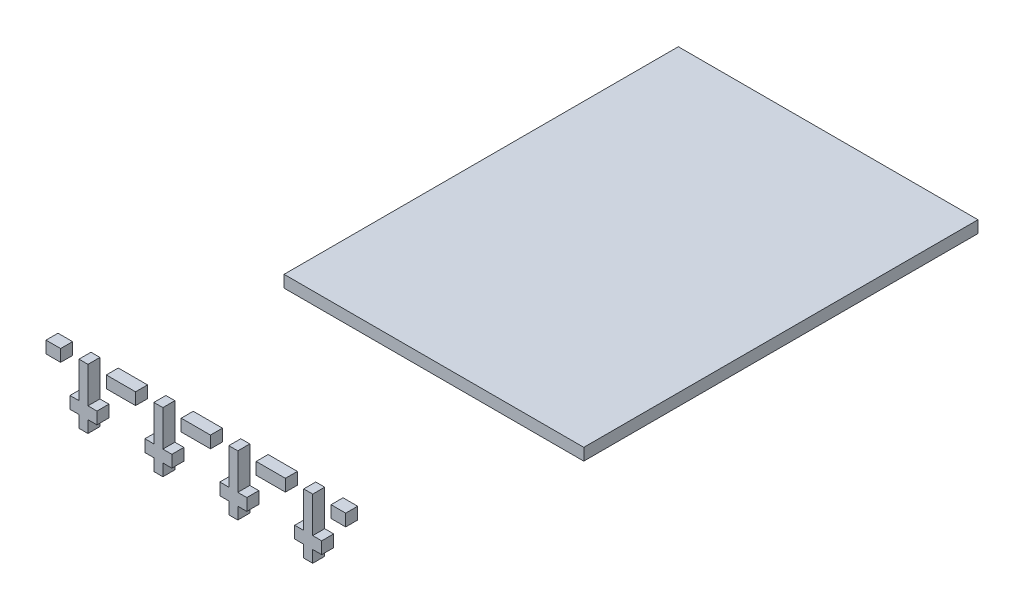
SolidWorks part; units mm, degrees
ref_plane "Front Plane" through (0, 0, 0) normal (0, 0, 1) x (1, 0, 0)
ref_plane "Top Plane" through (0, 0, 0) normal (0, 1, 0) x (1, 0, 0)
ref_plane "Right Plane" through (0, 0, 0) normal (1, 0, 0) x (0, 0, -1)
sketch "Sketch3" plane through (0, 0, 0) normal (0, 1, 0) x (1, 0, 0)
  line L0 (8.1353, -185.9578) -> (8.1353, -276.4821) construction
  line L1 (-16.8647, -185.9578) -> (-16.8647, -276.4821) construction
  line L2 (-16.8647, -222.3177) -> (83.1353, -222.3177)
  line L3 (-16.8647, -218.3177) -> (83.1353, -218.3177)
  line L4 (33.1353, -185.9578) -> (33.1353, -276.4821) construction
  line L5 (83.1353, -185.9578) -> (83.1353, -276.4821) construction
  line L6 (3.2529, -185.9578) -> (3.2529, -282.554) construction
  line L7 (-4.3647, -185.9578) -> (-4.3647, -282.554) construction
  line L8 (13.0176, -282.554) -> (13.0176, -185.9578) construction
  line L9 (28.2529, -185.9578) -> (28.2529, -282.554) construction
  line L10 (58.1353, -185.9578) -> (58.1353, -276.4821) construction
  line L11 (-16.8647, -220.3177) -> (83.1353, -220.3177) construction
  line L12 (38.0176, -282.554) -> (38.0176, -185.9578) construction
  line L13 (53.2529, -185.9578) -> (53.2529, -282.554) construction
  line L14 (20.6353, -282.554) -> (20.6353, -185.9578) construction
  line L15 (63.0176, -282.554) -> (63.0176, -185.9578) construction
  line L16 (78.2529, -185.9578) -> (78.2529, -282.554) construction
  line L17 (45.6353, -185.9578) -> (45.6353, -282.554) construction
  line L18 (-11.9824, -185.9578) -> (-11.9824, -282.554) construction
  line L19 (-2.8647, -222.3177) -> (-5.8647, -222.3177)
  line L20 (-2.8647, -222.3177) -> (-2.8647, -218.3177)
  line L21 (-2.8647, -218.3177) -> (-5.8647, -218.3177)
  line L22 (-5.8647, -222.3177) -> (-5.8647, -218.3177)
  line L23 (-2.8647, -222.3177) -> (-5.8647, -218.3177) construction
  line L24 (-2.8647, -218.3177) -> (-5.8647, -222.3177) construction
  line L25 (22.1353, -222.3177) -> (19.1353, -222.3177)
  line L26 (22.1353, -222.3177) -> (22.1353, -218.3177)
  line L27 (22.1353, -218.3177) -> (19.1353, -218.3177)
  line L28 (19.1353, -222.3177) -> (19.1353, -218.3177)
  line L29 (22.1353, -222.3177) -> (19.1353, -218.3177) construction
  line L30 (22.1353, -218.3177) -> (19.1353, -222.3177) construction
  line L31 (70.6353, -185.9578) -> (70.6353, -282.554) construction
  line L32 (-16.8647, -218.3177) -> (-16.8647, -222.3177)
  line L33 (47.1353, -222.3177) -> (44.1353, -222.3177)
  line L34 (47.1353, -222.3177) -> (47.1353, -218.3177)
  line L35 (47.1353, -218.3177) -> (44.1353, -218.3177)
  line L36 (44.1353, -222.3177) -> (44.1353, -218.3177)
  line L37 (47.1353, -222.3177) -> (44.1353, -218.3177) construction
  line L38 (47.1353, -218.3177) -> (44.1353, -222.3177) construction
  line L39 (72.1353, -222.3177) -> (69.1353, -222.3177)
  line L40 (72.1353, -222.3177) -> (72.1353, -218.3177)
  line L41 (72.1353, -218.3177) -> (69.1353, -218.3177)
  line L42 (69.1353, -222.3177) -> (69.1353, -218.3177)
  line L43 (72.1353, -222.3177) -> (69.1353, -218.3177) construction
  line L44 (72.1353, -218.3177) -> (69.1353, -222.3177) construction
  line L45 (-11.9824, -218.3177) -> (-11.9824, -222.3177)
  line L46 (3.2529, -218.3177) -> (3.2529, -222.3177)
  line L47 (13.0176, -218.3177) -> (13.0176, -222.3177)
  line L48 (28.2529, -218.3177) -> (28.2529, -222.3177)
  line L49 (38.0176, -218.3177) -> (38.0176, -222.3177)
  line L50 (53.2529, -218.3177) -> (53.2529, -222.3177)
  line L51 (63.0176, -218.3177) -> (63.0176, -222.3177)
  line L52 (78.2529, -218.3177) -> (78.2529, -222.3177)
  line L53 (83.1353, -218.3177) -> (83.1353, -222.3177)
  line L55 (-2.8647, -218.3177) -> (0.1353, -218.3177)
  line L56 (-2.8647, -218.3177) -> (-2.8647, -222.3177)
  line L57 (-2.8647, -222.3177) -> (0.1353, -222.3177)
  line L58 (0.1353, -218.3177) -> (0.1353, -222.3177)
  line L59 (-1.3647, -222.3177) -> (-1.3647, -218.3177) construction
  line L60 (-2.8647, -220.3177) -> (0.1353, -220.3177) construction
  line L61 (-5.8647, -218.3177) -> (-8.8647, -218.3177)
  line L62 (-5.8647, -218.3177) -> (-5.8647, -222.3177)
  line L63 (-5.8647, -222.3177) -> (-8.8647, -222.3177)
  line L64 (-8.8647, -218.3177) -> (-8.8647, -222.3177)
  line L65 (-7.3647, -222.3177) -> (-7.3647, -218.3177) construction
  line L66 (-5.8647, -220.3177) -> (-8.8647, -220.3177) construction
  line L67 (19.1353, -218.3177) -> (16.1353, -218.3177)
  line L68 (19.1353, -218.3177) -> (19.1353, -222.3177)
  line L69 (19.1353, -222.3177) -> (16.1353, -222.3177)
  line L70 (16.1353, -218.3177) -> (16.1353, -222.3177)
  line L71 (17.6353, -222.3177) -> (17.6353, -218.3177) construction
  line L72 (19.1353, -220.3177) -> (16.1353, -220.3177) construction
  line L73 (22.1353, -218.3177) -> (25.1353, -218.3177)
  line L74 (22.1353, -218.3177) -> (22.1353, -222.3177)
  line L75 (22.1353, -222.3177) -> (25.1353, -222.3177)
  line L76 (25.1353, -218.3177) -> (25.1353, -222.3177)
  line L77 (23.6353, -222.3177) -> (23.6353, -218.3177) construction
  line L78 (22.1353, -220.3177) -> (25.1353, -220.3177) construction
  line L79 (44.1353, -218.3177) -> (41.1353, -218.3177)
  line L80 (44.1353, -218.3177) -> (44.1353, -222.3177)
  line L81 (44.1353, -222.3177) -> (41.1353, -222.3177)
  line L82 (41.1353, -218.3177) -> (41.1353, -222.3177)
  line L83 (42.6353, -222.3177) -> (42.6353, -218.3177) construction
  line L84 (44.1353, -220.3177) -> (41.1353, -220.3177) construction
  line L85 (47.1353, -218.3177) -> (50.1353, -218.3177)
  line L86 (47.1353, -218.3177) -> (47.1353, -222.3177)
  line L87 (47.1353, -222.3177) -> (50.1353, -222.3177)
  line L88 (50.1353, -218.3177) -> (50.1353, -222.3177)
  line L89 (48.6353, -222.3177) -> (48.6353, -218.3177) construction
  line L90 (47.1353, -220.3177) -> (50.1353, -220.3177) construction
  line L91 (72.1353, -218.3177) -> (75.1353, -218.3177)
  line L92 (72.1353, -218.3177) -> (72.1353, -222.3177)
  line L93 (72.1353, -222.3177) -> (75.1353, -222.3177)
  line L94 (75.1353, -218.3177) -> (75.1353, -222.3177)
  line L95 (73.6353, -222.3177) -> (73.6353, -218.3177) construction
  line L96 (72.1353, -220.3177) -> (75.1353, -220.3177) construction
  line L97 (69.1353, -218.3177) -> (66.1353, -218.3177)
  line L98 (69.1353, -218.3177) -> (69.1353, -222.3177)
  line L99 (69.1353, -222.3177) -> (66.1353, -222.3177)
  line L100 (66.1353, -218.3177) -> (66.1353, -222.3177)
  line L101 (67.6353, -222.3177) -> (67.6353, -218.3177) construction
  line L102 (69.1353, -220.3177) -> (66.1353, -220.3177) construction
  point P34 (-4.3647, -220.3177)
  point P41 (20.6353, -220.3177)
  point P50 (45.6353, -220.3177)
  point P55 (70.6353, -220.3177)
  point P128 (-7.3647, -220.3177)
  point P144 (17.6353, -220.3177)
  point P152 (23.6353, -220.3177)
  point P158 (73.6353, -220.3177)
  point P163 (-1.3647, -220.3177)
  point P164 (48.6353, -220.3177)
  point P167 (42.6353, -220.3177)
  point P215 (67.6353, -220.3177)
  dimension "D5" = 4
  dimension "D1" = 100
  dimension "D2" = 25
  dimension "D3" = 25
  dimension "D4" = 25
  dimension "D6" = 4.8824
  dimension "D7" = 4.8824
  dimension "D8" = 4.8824
  dimension "D9" = 4.8824
  dimension "D10" = 4.8824
  dimension "D11" = 4.8824
  dimension "D12" = 4.8824
  dimension "D13" = 4.8824
  dimension "D14" = 12.5
  dimension "D15" = 2
  dimension "D16" = 12.5
  dimension "D17" = 3
  dimension "D18" = 3
  dimension "D19" = 12.5
  dimension "D20" = 12.5
  dimension "D21" = 3
  dimension "D22" = 3
  dimension "D23" = 3
  dimension "D24" = 3
  dimension "D25" = 3
  dimension "D26" = 3
  dimension "D27" = 3
  dimension "D28" = 3
  dimension "D29" = 3
  dimension "D30" = 3
extrude "Boss-Extrude2" add sketch "Sketch3" along normal blind 4 separate body contours L45 L3 L32 L2 | L22 L2 L20 L3 | L47 L3 L46 L2 | L28 L2 L26 L3 | L49 L3 L48 L2 | L36 L2 L34 L3 | L51 L3 L50 L2 | L42 L2 L40 L3 | L53 L3 L52 L2 region at (-14.4236, 0, 220.3177) region at (-4.3647, 0, 220.3177) region at (8.1353, 0, 220.3177) region at (20.6353, 0, 220.3177) region at (33.1353, 0, 220.3177) region at (45.6353, 0, 220.3177) region at (58.1353, 0, 220.3177) region at (70.6353, 0, 220.3177) region at (80.6941, 0, 220.3177)
extrude "Boss-Extrude4" add sketch "Sketch3<6>" against normal blind 16 contours L22 L2 L20 L3 | L28 L2 L26 L3 | L36 L2 L34 L3 | L42 L2 L40 L3 region at (-4.3647, 0, 220.3177) region at (20.6353, 0, 220.3177) region at (45.6353, 0, 220.3177) region at (70.6353, 0, 220.3177)
sketch "Sketch3<6>" plane through (0, 0, 0) normal (0, 1, 0) x (1, 0, 0) same geometry as "Sketch3"
extrude "Boss-Extrude5" add sketch "Sketch3<7>" along normal blind 4 from offset 12 contours L3 L64 L2 L22 | L58 L3 L20 L2 | L3 L70 L2 L28 | L76 L3 L26 L2 | L3 L82 L2 L36 | L88 L3 L34 L2 | L3 L100 L2 L42 | L94 L3 L40 L2 region at (-7.3647, 0, 220.3177) region at (-1.3647, 0, 220.3177) region at (17.6353, 0, 220.3177) region at (23.6353, 0, 220.3177) region at (42.6353, 0, 220.3177) region at (48.6353, 0, 220.3177) region at (67.6353, 0, 220.3177) region at (73.6353, 0, 220.3177) offset against normal yes
sketch "Sketch3<7>" plane through (0, 0, 0) normal (0, 1, 0) x (1, 0, 0) same geometry as "Sketch3"
sketch "Sketch4" plane through (0, 0, 0) normal (0, 1, 0) x (1, 0, 0)
  line L1 (3.8456, -163.5816) -> (103.8456, -163.5816)
  line L2 (3.8456, -163.5816) -> (3.8456, -32.038)
  line L3 (3.8456, -32.038) -> (103.8456, -32.038)
  line L4 (103.8456, -163.5816) -> (103.8456, -32.038)
  line L5 (53.8456, -32.038) -> (53.8456, -163.5816) construction
  line L6 (3.8456, -97.8098) -> (103.8456, -97.8098) construction
  point P56 (53.8456, -97.8098)
  dimension "D1" = 100
  dimension "D2" = 131.5436
extrude "Boss-Extrude6" add sketch "Sketch4" along normal blind 4 separate body
equation "\"L1\"=152.997"
equation "\"H\"= 200"
equation "\"L\" = 300"
equation "\"nema_internal\"= 31"
equation "\"nema_external\"= 42.3"
equation "\"bars\"= 9.60"
equation "\"trehead_rods\"= 8"
equation "\"hole_nema\"= 3"
equation "\"D1@Sketch1\"=\"L\""
equation "\"D2@Sketch1\"=\"H\""
equation "\"D3@Sketch1\"=\"nema_external\""
equation "\"D4@Sketch1\"=\"nema_external\""
equation "\"D5@Sketch1\"=\"hole_nema\""
equation "\"D6@Sketch1\"=\"hole_nema\""
equation "\"D7@Sketch1\"=\"hole_nema\""
equation "\"D8@Sketch1\"=\"hole_nema\""
equation "\"D9@Sketch1\"=\"nema_internal\""
equation "\"D10@Sketch1\"=\"nema_internal\""
equation "\"D11@Sketch1\"=\"L\"/7"
equation "\"D12@Sketch1\"=\"L\"/3"
equation "\"D13@Sketch1\"=\"bars\""
equation "\"D14@Sketch1\"=\"bars\""
equation "\"D15@Sketch1\"=\"bars\""
equation "\"ring_dimension_max\" = 80"
equation "\"thik_material\"= 4"
equation "\"D17@Sketch1\"=\"bars\""
equation "\"D18@Sketch1\"=\"L\"/12"
equation "\"kerf\"= 1"
equation "\"D1@Boss-Extrude3\"=\"thik_material\""
equation "\"ring_b\"=100"
equation "\"D19@Sketch1\"=\"ring_b\"-3"
equation "\"D20@Sketch1\"=\"ring_b\""
equation "\"D5@Sketch3\"=\"thik_material\""
equation "\"D1@Sketch3\"=100"
equation "\"D2@Sketch3\"=\"D1@Sketch3\"/4"
equation "\"D3@Sketch3\"=\"D1@Sketch3\"/4"
equation "\"D4@Sketch3\"=\"D1@Sketch3\"/4"
equation "\"D6@Sketch3\"=(\"D1@Sketch3\"/17)-(\"kerf\")"
equation "\"D7@Sketch3\"=(\"D1@Sketch3\"/17)-(\"kerf\")"
equation "\"D8@Sketch3\"=(\"D1@Sketch3\"/17)-(\"kerf\")"
equation "\"D9@Sketch3\"=(\"D1@Sketch3\"/17)-(\"kerf\")"
equation "\"D10@Sketch3\"=(\"D1@Sketch3\"/17)-(\"kerf\")"
equation "\"D11@Sketch3\"=(\"D1@Sketch3\"/17)-(\"kerf\")"
equation "\"D12@Sketch3\"=\"D1@Sketch3\"/17-(\"kerf\")"
equation "\"D13@Sketch3\"=\"D1@Sketch3\"/17-(\"kerf\")"
equation "\"D14@Sketch3\"=\"D1@Sketch3\"/8"
equation "\"D15@Sketch3\"=\"thik_material\"/2"
equation "\"D16@Sketch3\"=\"D1@Sketch3\"/8"
equation "\"D17@Sketch3\"=\"hole_nema\""
equation "\"D18@Sketch3\"=\"hole_nema\""
equation "\"D19@Sketch3\"=\"D1@Sketch3\"/8"
equation "\"D20@Sketch3\"=\"D1@Sketch3\"/8"
equation "\"D21@Sketch3\"=\"hole_nema\""
equation "\"D22@Sketch3\"=\"hole_nema\""
equation "\"D1@Boss-Extrude2\"=\"thik_material\""
equation "\"D1@Boss-Extrude4\"=\"thik_material\"+12"
equation "\"D23@Sketch3\"=\"hole_nema\""
equation "\"D24@Sketch3\"=\"hole_nema\""
equation "\"D25@Sketch3\"=\"hole_nema\""
equation "\"D26@Sketch3\"=\"hole_nema\""
equation "\"D27@Sketch3\"=\"hole_nema\""
equation "\"D28@Sketch3\"=\"hole_nema\""
equation "\"D29@Sketch3\"=\"hole_nema\""
equation "\"D30@Sketch3\"=\"hole_nema\""
equation "\"D1@Boss-Extrude6\"=\"thik_material\""
equation "\"D1@Sketch4\"=\"D1@sketch3\""
